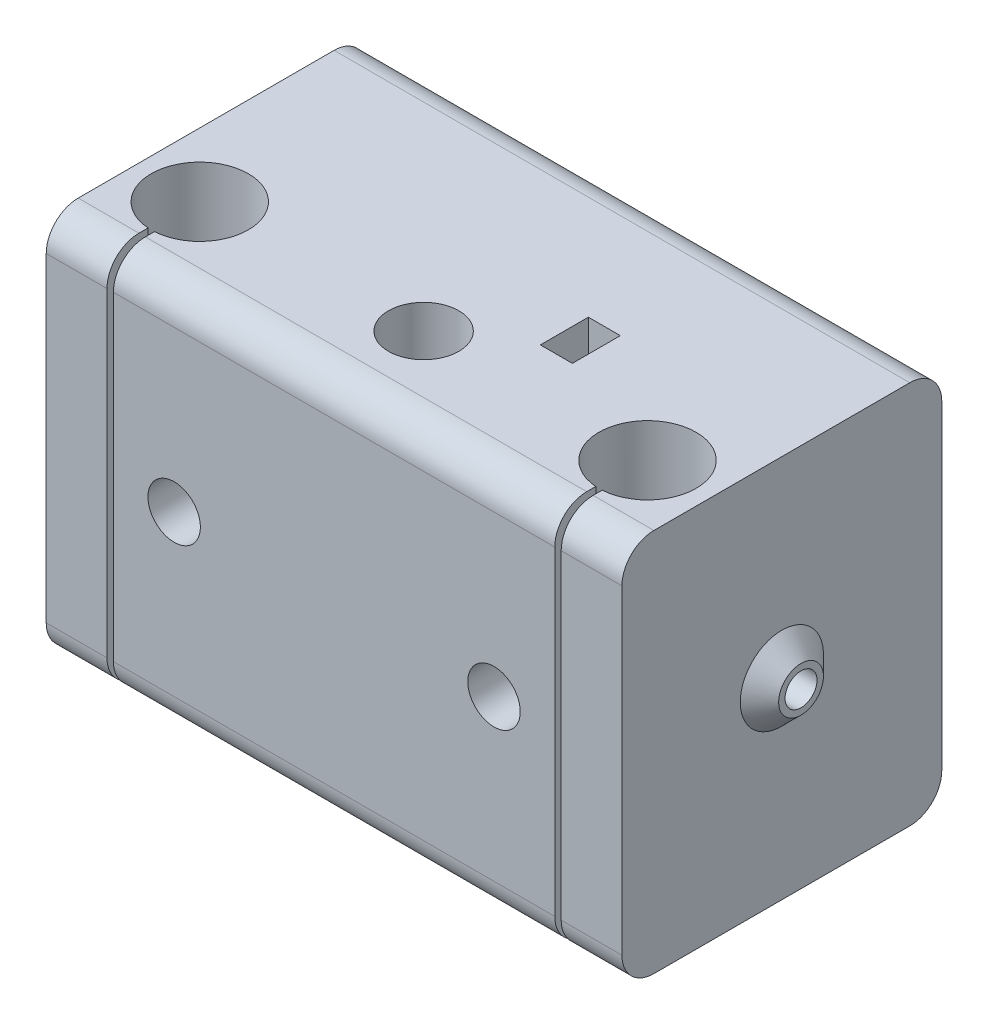
SolidWorks part; units mm, degrees
ref_plane "Front Plane" through (0, 0, 0) normal (0, 0, 1) x (1, 0, 0)
ref_plane "Top Plane" through (0, 0, 0) normal (0, 1, 0) x (1, 0, 0)
ref_plane "Right Plane" through (0, 0, 0) normal (1, 0, 0) x (0, 0, -1)
sketch "Sketch1" plane through (0, 0, 0) normal (1, 0, 0) x (0, 0, -1)
  line L1 (-20, -30) -> (20, -30)
  line L2 (-25, -25) -> (-25, 25)
  line L3 (-20, 30) -> (20, 30)
  line L4 (25, -25) -> (25, 25)
  line L5 (-25, -30) -> (25, 30) construction
  line L6 (-25, 30) -> (25, -30) construction
  arc A0 (-20, -30) -> (-25, -25) centre (-20, -25) cw
  arc A1 (20, -30) -> (25, -25) centre (20, -25) ccw
  arc A2 (20, 30) -> (25, 25) centre (20, 25) cw
  arc A3 (-25, 25) -> (-20, 30) centre (-20, 25) cw
  point P0 (0, 0)
  dimension "D3" = 5
  dimension "D1" = 60
  dimension "D2" = 50
extrude "Boss-Extrude1" add sketch "Sketch1" along normal blind 90
sketch "Sketch2" plane through (0, 30, 0) normal (0, 1, 0) x (1, 0, 0)
  line L0 (0, -11) -> (90, -11) construction
  line L1 (0, 20) -> (0, -20) construction
  line L2 (90, 20) -> (90, -20) construction
  line L3 (90, -25) -> (0, -25) construction
  circle A0 centre (10, -11) radius 7.6
  circle A1 centre (80, -11) radius 7.6
  circle A2 centre (45, -11) radius 5.5
  point P12 (45, -11)
  dimension "D1" = 15.2
  dimension "D2" = 70
  dimension "D5" = 11
  dimension "D3" = 35
  dimension "D4" = 14
extrude "Cut-Extrude1" cut sketch "Sketch2" against normal blind 90
sketch "Sketch3" plane through (0, 0, 25) normal (0, 0, 1) x (1, 0, 0)
  line L0 (0, 0) -> (90, 0) construction
  line L1 (0, 25) -> (0, -25) construction
  line L2 (90, 25) -> (90, -25) construction
  circle A0 centre (20, 0) radius 4.1
  circle A1 centre (70, 0) radius 4.1
  point P10 (45, 0)
  dimension "D2" = 8.2
  dimension "D3" = 8.2
  dimension "D1" = 50
  dimension "D4" = 25
extrude "Cut-Extrude2" cut sketch "Sketch3" against normal blind 90
sketch "Sketch10" plane through (0, 30, 0) normal (0, 1, 0) x (1, 0, 0)
  line L0 (10, -11) -> (10, -42.3505)
  line L1 (80, -11) -> (80, -42.3505)
extrude "Cut-Extrude-Thin1" cut sketch "Sketch10" against normal blind 70 thin thin type mid plane wall 1
sketch "Sketch11" plane through (0, -30, 0) normal (0, -1, 0) x (-1, 0, 0)
  circle A0 centre (-45, -11) radius 11.5
  dimension "D1" = 23
extrude "Cut-Extrude6" cut sketch "Sketch11" against normal blind 7
sketch "Sketch12" plane through (0, -23, 0) normal (0, -1, 0) x (-1, 0, 0)
  line L0 (-45, -11) -> (-45, -19) construction
  circle A0 centre (-45, -19) radius 1.95
  circle A1 centre (-53, -11) radius 1.95
  circle A2 centre (-45, -3) radius 1.95
  circle A3 centre (-37, -11) radius 1.95
  point P13 (-45, -11)
  dimension "D1" = 3.9
  dimension "D2" = 8
  dimension "D3" = 4
extrude "Cut-Extrude7" cut sketch "Sketch12" against normal blind 15
sketch "Sketch16" plane through (0, 0, -25) normal (0, 0, -1) x (-1, 0, 0)
  circle A0 centre (-70, 0) radius 4.1
  circle A1 centre (-20, 0) radius 4.1
extrude "Boss-Extrude2" add sketch "Sketch16" against normal blind 3
fillet "Fillet1" radius 2 2 edges at (65.9, 0, -22) (15.9, 0, -22)
sketch "Sketch17" plane through (90, 0, 0) normal (1, 0, 0) x (0, 0, -1)
  circle A0 centre (0, 0) radius 2.5
  dimension "D1" = 5
extrude "Cut-Extrude8" cut sketch "Sketch17" against normal blind 30
sketch "Sketch18" plane through (0, 30, 0) normal (0, 1, 0) x (1, 0, 0)
  line L0 (90, 20) -> (90, -20) construction
  line L1 (56, -3.75) -> (61, -3.75)
  line L2 (56, -3.75) -> (56, 3.75)
  line L3 (56, 3.75) -> (61, 3.75)
  line L4 (61, -3.75) -> (61, 3.75)
  line L5 (56, -3.75) -> (61, 3.75) construction
  line L6 (56, 3.75) -> (61, -3.75) construction
  point P0 (58.5, 0)
  point P7 (61, 0)
  point P8 (90, 0)
  dimension "D1" = 29
  dimension "D2" = 5
  dimension "D3" = 7.5
  dimension "D4" = 0
extrude "Cut-Extrude9" cut sketch "Sketch18" against normal blind 44
sketch "Sketch19" plane through (90, 0, 0) normal (1, 0, 0) x (0, 0, -1)
  circle A0 centre (0, 0) radius 2.5
  circle A1 centre (0, 0) radius 3.5
  dimension "D1" = 7
extrude "Boss-Extrude3" add sketch "Sketch19" along normal blind 3
chamfer "Chamfer1" distance 3 angle 45 1 edges at (90, 0, 3.5)
